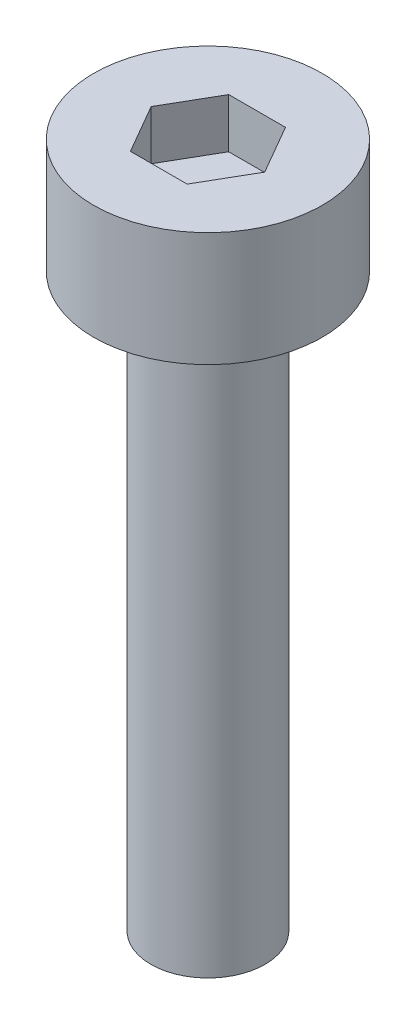
SolidWorks part; units mm, degrees
ref_plane "Front Plane" through (0, 0, 0) normal (0, 0, 1) x (1, 0, 0)
ref_plane "Top Plane" through (0, 0, 0) normal (0, 1, 0) x (1, 0, 0)
ref_plane "Right Plane" through (0, 0, 0) normal (1, 0, 0) x (0, 0, -1)
sketch "Sketch1" plane through (0, 0, 0) normal (0, 1, 0) x (1, 0, 0)
  circle A0 centre (0, 0) radius 1.5
  dimension "D1" = 3
extrude "ScrewShaft" add sketch "Sketch1" along normal blind 15
sketch "Sketch2" plane through (0, 15, 0) normal (0, 1, 0) x (1, 0, 0)
  circle A0 centre (0, 0) radius 3
  dimension "D1" = 6
extrude "Boss-Extrude2" add sketch "Sketch2" along normal blind 3
sketch "Sketch3" plane through (0, 18, 0) normal (0, 1, 0) x (1, 0, 0)
  line L0 (0, 0) -> (0, 1.29) construction
  line L1 (1.4896, 0) -> (0.7448, 1.29)
  line L2 (0.7448, 1.29) -> (-0.7448, 1.29)
  line L3 (-0.7448, 1.29) -> (-1.4896, 0)
  line L4 (-1.4896, 0) -> (-0.7448, -1.29)
  line L5 (-0.7448, -1.29) -> (0.7448, -1.29)
  line L6 (0.7448, -1.29) -> (1.4896, 0)
  circle A0 centre (0, 0) radius 1.29 construction
  dimension "D1" = 2.58
extrude "Cut-Extrude1" cut sketch "Sketch3" against normal blind 1.3
equation "\"X-ROD-SPACING\"=45"
equation "\"Y-ROD-SPACING\"=75"
equation "\"Z-ROD-SPACING\"=17.5"
equation "\"Y-BED-OFFSET\"=2"
equation "\"Y-BED-ROD-INSET\"=3.5"
equation "\"T-SLOT-NUT-FILLET-RADIUS\"=0.5"
equation "\"T-SLOT-SCREW-SHAFT-RADIUS\"=1.55"
equation "\"T-SLOT-SCREW-SHAFT-CUTOUT-LENGTH\"=11"
equation "\"T-SLOT-NUT-DEPTH\"=3.5"
equation "\"T-SLOT-NUT-WIDTH\"=2.85"
equation "\"T-SLOT-NUT-END-DISTANCE\"=8"
equation "\"ACRYLIC-THICKNESS\"=10"
equation "\"ACRYLIC-THICKNESS2\"=4.5"
equation "\"ACRYLIC-TAB-CUTOUT-SIZE\"=\"ACRYLIC-THICKNESS\"+\"ACRYLIC-TAB-TOLERANCE\"*2"
equation "\"ACRYLIC-TAB-WIDTH\"=\"ACRYLIC-THICKNESS\""
equation "\"ACRYLIC-M3-HOLE\"=2.9"
equation "\"SMOOTHROD-CAP-SCREW-DISTANCE\"=20"
equation "\"FRAME-WIDTH-INNER\"=370"
equation "\"NEMA17-HOLE-SPACING\"=31"
equation "\"NEMA17-CENTRAL-CUTOUT\"=22.5"
equation "\"Z-BRACKET-REACH\"=55"
equation "\"TOP-BRACKET-SPACING\"=40"
equation "\"SMOOTHROD-X-LENGTH\"=350"
equation "\"SMOOTHROD-Y-LENGTH\"=350"
equation "\"SMOOTHROD-Z-LENGTH\"=350"
equation "\"SMOOTHROD-TIGHTENING-HEADROOM\"=.25"
equation "\"LEADSCREW-Z-LENGTH\"=300"
equation "\"SCREW-LENGTH-FRAME\"=\"ACRYLIC-THICKNESS\" + 10"
equation "\"SCREW-HEAD-RADIUS\"=6"
equation "\"PRINTED-X-SMOOTHROD-DIAMETER\"=9.0"
equation "\"PRINTED-X-SMOOTHROD-CUTOUT\"=10"
equation "\"PRINTED-X-BASE-HEIGHT\"=10"
equation "\"PRINTED-LM8UU-CUTOUT-SIZE\"=15.5"
equation "\"PRINTED-LM8UU-CUTOUT-LENGTH\"=24.5"
equation "\"PRINTED-X-IDLER-HEIGHT\"=16"
equation "\"PSU-MOUNTING-WIDTH\"=95"
equation "\"PSU-MOUNTING-HEIGHT\"=177"
equation "\"D1@ScrewShaft\"=\"SCREW-LENGTH-MOTOR\""
equation "\"D1@Sketch2\"=\"SCREW-HEAD-RADIUS\""
equation "\"Y-BED-SCREW-SPACING\"=209"
equation "\"Y-BED-SCREW-CUTOUT-SLOT-HEIGHT\"=2"
equation "\"Z-ROD-INSET\"=13.5"
equation "\"SCREW-LENGTH-MOTOR\"=\"ACRYLIC-THICKNESS\" + 5"
equation "\"Y-BELT-TO-ROD-DISTANCE\"=20"
equation "\"SPOOL-HOLDER-ROD-SPACING\"=150"
